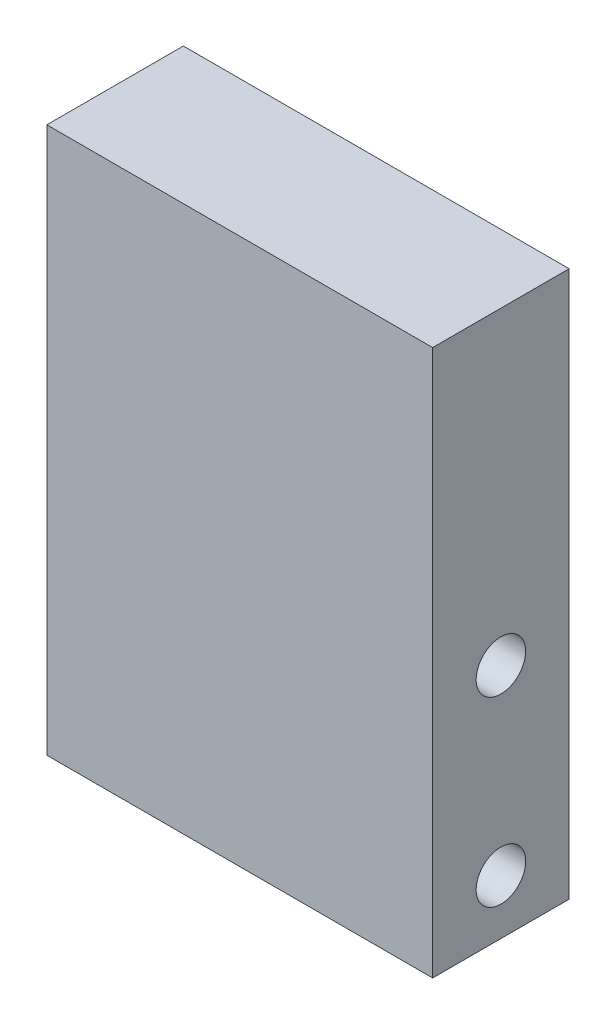
SolidWorks part; units mm, degrees
material "6061 Alloy"
ref_plane "Front Plane" through (0, 0, 0) normal (0, 0, 1) x (1, 0, 0)
ref_plane "Top Plane" through (0, 0, 0) normal (0, 1, 0) x (1, 0, 0)
ref_plane "Right Plane" through (0, 0, 0) normal (1, 0, 0) x (0, 0, -1)
sketch "Sketch1" plane through (0, 0, 0) normal (0, 0, 1) x (1, 0, 0)
  line L1 (-13.462, 19.05) -> (13.462, 19.05)
  line L2 (-13.462, 19.05) -> (-13.462, -19.05)
  line L3 (-13.462, -19.05) -> (13.462, -19.05)
  line L4 (13.462, 19.05) -> (13.462, -19.05)
  dimension "D1" = 13.462
  dimension "D2" = 13.462
  dimension "D3" = 19.05
  dimension "D4" = 19.05
extrude "Boss-Extrude1" add sketch "Sketch1" along normal mid plane 9.525
hole_wizard "#8-32 Tapped Hole1" positions "Sketch3" profile "Sketch2" tap size "#8-32" standard "ANSI Inch" end condition up to next
sketch "Sketch3" plane through (13.462, 0, 0) normal (1, 0, 0) x (0, 0, -1)
  line L0 (-4.7625, -19.05) -> (4.7625, -19.05) construction
  line L1 (4.7625, -19.05) -> (4.7625, 19.05) construction
  point P0 (0, -15.24)
  point P6 (0, -2.54)
  dimension "D1" = 3.81
  dimension "D2" = 12.7
  dimension "D3" = 4.7625
cosmetic thread "Hole Thread1" parameters "D2"=4.1656
sketch "Sketch2" plane through (13.462, -15.24, 0) normal (0, 1, 0) x (0, 0, -1)
  line L0 (0, 0) -> (0, 26.924)
  line L1 (0, 26.924) -> (1.7272, 26.924)
  line L2 (1.7272, 26.924) -> (1.7272, 0)
  line L5 (1.7272, 0) -> (0, 0)
  line L11 (0, -6.35) -> (0, 107.95) construction
  dimension "Thru Tap Drill Dia." = 3.4544
  dimension "Thru Tap Drill Depth" = 26.924
cosmetic thread "Hole Thread2" parameters "D2"=4.1656
